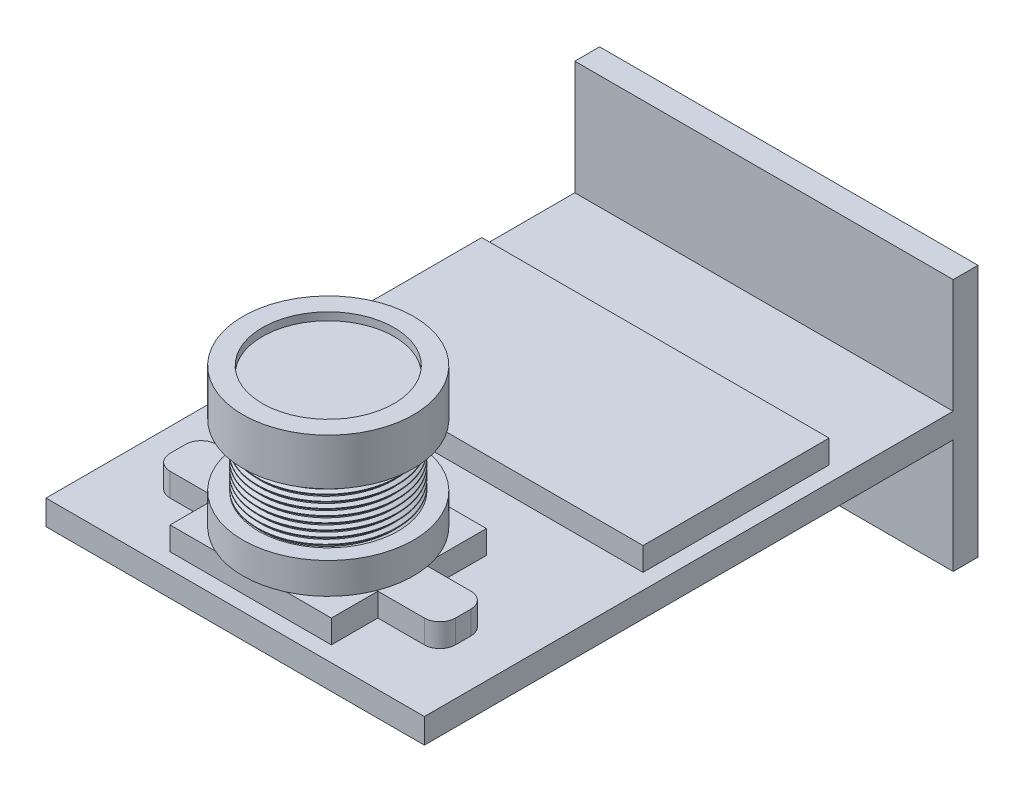
SolidWorks part; units mm, degrees
ref_plane "Front Plane" through (0, 0, 0) normal (0, 0, 1) x (1, 0, 0)
ref_plane "Top Plane" through (0, 0, 0) normal (0, 1, 0) x (1, 0, 0)
ref_plane "Right Plane" through (0, 0, 0) normal (1, 0, 0) x (0, 0, -1)
sketch "Sketch1" plane through (0, 0, 0) normal (0, 0, 1) x (1, 0, 0)
  line L1 (-14.1632, 2.419) -> (10.2368, 2.419)
  line L2 (-14.1632, 2.419) -> (-14.1632, 0.819)
  line L3 (-14.1632, 0.819) -> (10.2368, 0.819)
  line L4 (10.2368, 2.419) -> (10.2368, 0.819)
  dimension "D1" = 24.4
  dimension "D2" = 1.6
extrude "Boss-Extrude1" add sketch "Sketch1" along normal blind 34.1
sketch "Sketch2" plane through (0, 2.419, 0) normal (0, 1, 0) x (1, 0, 0)
  line L0 (10.2368, -34.1) -> (-14.1632, -34.1) construction
  line L1 (3.2368, -33.1) -> (-7.1632, -33.1)
  line L2 (3.2368, -33.1) -> (3.2368, -23.1)
  line L3 (3.2368, -23.1) -> (-7.1632, -23.1)
  line L4 (-7.1632, -33.1) -> (-7.1632, -23.1)
  line L5 (-14.1632, -34.1) -> (-14.1632, 0) construction
  line L6 (10.2368, -34.1) -> (10.2368, 0) construction
  dimension "D1" = 1
  dimension "D2" = 7
  dimension "D3" = 7
  dimension "D4" = 10
extrude "Boss-Extrude2" add sketch "Sketch2" along normal blind 1.5
sketch "Sketch3" plane through (0, 3.919, 0) normal (0, 1, 0) x (1, 0, 0)
  line L0 (10.2368, -34.1) -> (10.2368, 0) construction
  line L1 (7.2368, -30.1) -> (-11.1632, -30.1)
  line L2 (7.2368, -30.1) -> (7.2368, -27.1)
  line L3 (7.2368, -27.1) -> (-11.1632, -27.1)
  line L4 (-11.1632, -30.1) -> (-11.1632, -27.1)
  line L5 (-14.1632, -34.1) -> (-14.1632, 0) construction
  line L6 (10.2368, -34.1) -> (-14.1632, -34.1) construction
  dimension "D1" = 3
  dimension "D2" = 3
  dimension "D3" = 4
  dimension "D4" = 3
extrude "Boss-Extrude3" add sketch "Sketch3" against normal blind 1.5
fillet "Fillet1" radius 1 4 edges at (7.2368, 3.169, 30.1) (7.2368, 3.169, 27.1) (-11.1632, 3.169, 30.1) (-11.1632, 3.169, 27.1)
sketch "Sketch4" plane through (0, 3.919, 0) normal (0, 1, 0) x (1, 0, 0)
  line L0 (-7.1632, -30.1) -> (-7.1632, -33.1) construction
  line L1 (-7.1632, -33.1) -> (3.2368, -33.1) construction
  circle A0 centre (-1.9632, -28.1) radius 5.5
  dimension "D1" = 5.2
  dimension "D2" = 5
  dimension "D3" = 11
extrude "Boss-Extrude4" add sketch "Sketch4" along normal blind 2
sketch "Sketch5" plane through (0, 5.919, 0) normal (0, 1, 0) x (1, 0, 0)
  circle A0 centre (-1.9632, -28.1) radius 4.5
  dimension "D1" = 9
extrude "Boss-Extrude5" add sketch "Sketch5" along normal blind 4
thread "Thread1" pitch 0.4 method cut profile "Thread Profile1" start angle 0, offset 0, length 0, pitch 0.4, diameter 9
ref_plane "Plane1" through (-6.4632, 9.919, 28.1) normal (0, 0, 1) x (-1, 0, 0)
sketch "Thread Profile1" plane through (-6.4632, 9.919, 28.1) normal (0, 0, 1) x (-1, 0, 0)
  line L0 (0, 0) -> (0, 0.4) construction
  line L11 (0, 0) -> (0, 0.35)
  line L12 (0, 0.35) -> (-0.2165, 0.225)
  line L13 (-0.2165, 0.225) -> (-0.2165, 0.125)
  line L15 (-0.2165, 0.125) -> (0, 0)
  line L17 (-0.2165, 0.175) -> (0, 0.175) construction
  point P2 (0, 0)
  dimension "Pitch" = 0.4
  dimension "Profile_Angle" = 60
  dimension "Profile_Land" = 0.1
  dimension "Profile_Height" = 0.2165
sketch "Sketch9" plane through (0, 9.919, 0) normal (0, 1, 0) x (1, 0, 0)
  circle A0 centre (-1.9632, -28.1) radius 5.5
  dimension "D1" = 11
extrude "Boss-Extrude6" add sketch "Sketch9" along normal blind 3
sketch "Sketch11" plane through (0, 12.919, 0) normal (0, 1, 0) x (1, 0, 0)
  circle A0 centre (-1.9632, -28.1) radius 4.2466
extrude "Cut-Extrude1" cut sketch "Sketch11" against normal blind 0.5
sketch "Sketch12" plane through (0, 2.419, 0) normal (0, 1, 0) x (1, 0, 0)
  line L0 (-14.1632, -34.1) -> (-14.1632, 0) construction
  line L1 (9.2368, -19) -> (-13.1632, -19)
  line L2 (9.2368, -19) -> (9.2368, -7)
  line L3 (9.2368, -7) -> (-13.1632, -7)
  line L4 (-13.1632, -19) -> (-13.1632, -7)
  line L5 (10.2368, 0) -> (-14.1632, 0) construction
  dimension "D1" = 22.4
  dimension "D2" = 1
  dimension "D3" = 7
  dimension "D4" = 12
extrude "Boss-Extrude7" add sketch "Sketch12" along normal blind 1.5
sketch "Sketch13" plane through (0, 0.819, 0) normal (0, -1, 0) x (1, 0, 0)
  line L0 (-14.1632, 34.1) -> (-14.1632, 0) construction
  line L1 (-11.9632, 26.1) -> (8.0368, 26.1)
  line L2 (-11.9632, 26.1) -> (-11.9632, 6.1)
  line L3 (-11.9632, 6.1) -> (8.0368, 6.1)
  line L4 (8.0368, 26.1) -> (8.0368, 6.1)
  line L5 (-14.1632, 34.1) -> (10.2368, 34.1) construction
  dimension "D1" = 20
  dimension "D2" = 2.2
  dimension "D3" = 20
  dimension "D4" = 8
extrude "Boss-Extrude8" add sketch "Sketch13" along normal blind 1.5
sketch "Sketch14" plane through (0, 0, 0) normal (0, 0, -1) x (-1, 0, 0)
  line L0 (14.1632, 0.819) -> (-10.2368, 0.819) construction
  line L5 (-10.2368, -6.531) -> (14.1632, -6.531)
  line L6 (-10.2368, -6.531) -> (-10.2368, 9.769)
  line L7 (-10.2368, 9.769) -> (14.1632, 9.769)
  line L8 (14.1632, -6.531) -> (14.1632, 9.769)
  dimension "D1" = 24.4
  dimension "D2" = 16.3
  dimension "D3" = 7.35
extrude "Boss-Extrude9" add sketch "Sketch14" along normal blind 1.6
